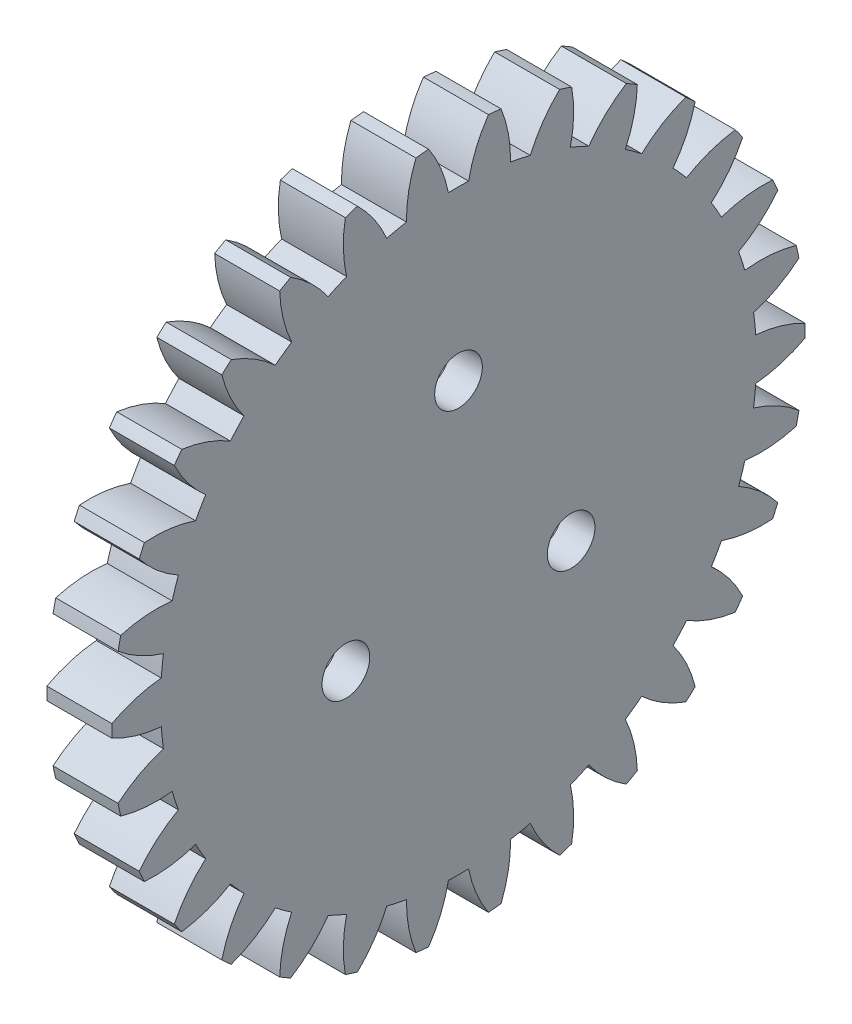
SolidWorks part; units mm, degrees
material "ﾎﾟﾘｵｷｼﾒﾁﾚﾝ(POM)ｱｾﾀｰﾙ共重合体"
ref_plane "Plane1" through (0, 0, 0) normal (0, 0, 1) x (1, 0, 0)
ref_plane "Plane2" through (0, 0, 0) normal (0, 1, 0) x (1, 0, 0)
ref_plane "Plane3" through (0, 0, 0) normal (1, 0, 0) x (0, 0, -1)
other "Configuration Table"
sketch "HoldingSke" plane through (0, 0, 0) normal (0, 1, 0) x (1, 0, 0)
  line L0 (0, 0) -> (0.866, -0.5)
  line L1 (-15, 0) -> (100, 0) construction
  line L2 (0, 0) -> (-2.1039, 2.3779)
  line L3 (0, 0) -> (-11.863, 4.5341)
  line L4 (0, 0) -> (7.479, 4.318)
  line L5 (0, 0) -> (-46.8476, -17.4728)
  line L6 (0, 0) -> (-2.4869, -1.6779)
  line L7 (-2.1039, 2.3779) -> (8.6586, 51.2059)
  line L8 (-76.2, 54.61) -> (-75.2, 54.61)
  line L9 (-71.009, 38.7566) -> (-53.1078, 45.2721)
  line L10 (-76.2, 71.12) -> (104.1128, 71.12)
  line L11 (0, 0) -> (-3, 0)
  line L12 (-76.2, 101.6) -> (-76.162, 101.6)
  line L13 (24.9733, 27.94) -> (52.9518, 28.4284)
  line L14 (24.9733, 27.94) -> (24.9743, 27.94)
  line L15 (24.9733, 27.94) -> (100.4006, 29.5858)
  line L16 (-63.627, -1) -> (-12.827, -1)
  circle A0 centre (0, 0) radius 4
  circle A1 centre (0, 0) radius 13.749
  circle A2 centre (0, 0) radius 37.5
  circle A3 centre (0, 0) radius 4
  dimension "MHD" = 27.498
  dimension "Hub_dia" = 75
  dimension "Bore" = 8
  dimension "MBD" = 8
  dimension "Num_teeth" = 30
  dimension "Pitch" = 1
  dimension "Overall_len" = 50
  dimension "Show_teeth" = 30
  dimension "Thickness" = 3
  dimension "OAL" = 50.0001
  dimension "T_dim" = 1
  dimension "Ap" = 20
  dimension "H" = 19.05
  dimension "Pitch_radius" = 180.3128
  dimension "Width" = 3
  dimension "Backlash" = 0.038
  dimension "Addendum_fac" = 1
  dimension "Dedendum_fac" = 1.25
  dimension "Clearance_fac" = 0.25
  dimension "Dedendum_add" = 0.001
  dimension "Module" = 1
sketch "BasProSke" plane through (0, 0, 0) normal (0, 1, 0) x (1, 0, 0)
  line L0 (-10, 0) -> (60, 0) construction
  line L1 (0, 0) -> (0, 16)
  line L2 (0, 0) -> (3, 0)
  line L3 (3, 0) -> (3, 16)
  line L4 (3, 16) -> (0, 16)
  dimension "Thickness" = 3
  dimension "Diameter" = 32
revolve "Base-Revolve" add sketch "BasProSke" angle 360 about L0
sketch "TooCutSke" plane through (0, 0, 0) normal (1, 0, 0) x (0, 0, -1)
  line L1 (0, 0) -> (0, 107) construction
  line L2 (0, 0) -> (-0.8515, 14.9758) construction
  line L3 (0, 0) -> (-3.1323, 29.8014) construction
  line L4 (-0.8515, 14.9758) -> (-1.5661, 14.9007) construction
  arc A0 (0.4664, 13.7411) -> (-0.4664, 13.7411) centre (0, 0) ccw
  arc A1 (1.3975, 15.9644) -> (-1.3975, 15.9644) centre (0, 0) ccw
  circle A2 centre (0, 0) radius 15 construction
  circle A3 centre (0, 0) radius 14.0954 construction
  arc A4 (-0.4664, 13.7411) -> (-1.3975, 15.9644) centre (-6.3534, 12.5823) ccw
  arc A5 (1.3975, 15.9644) -> (0.4664, 13.7411) centre (6.3534, 12.5823) ccw
  dimension "Root_dia" = 27.498
  dimension "Overcut_dia" = 32.0508
  dimension "Pitch_dia" = 30
  dimension "Base_dia" = 28.1908
  dimension "Flank_rad" = 6
  dimension "Half_ang" = 6
  dimension "Half_CT" = 0.7185
extrude "ToothCut" cut sketch "TooCutSke" along normal through all
fillet "Breaks" [suppressed] radius 0.02 tangent propagation no
fillet "RootFillets" [suppressed] radius 0.251
pattern_circular "TeethCuts" count 30 every 12 about axis through (-10, 0, 0) along (1, 0, 0) of "ToothCut", "RootFillets", "Breaks"
sketch "HubNeaOneSke" plane through (0, 0, 0) normal (-1, 0, 0) x (0, 0, 1)
  circle A0 centre (0, 0) radius 13.749
  dimension "Diameter" = 27.498
extrude "HubNearOne" [suppressed] add sketch "HubNeaOneSke" along normal blind 47.0001
sketch "HubNeaBotSke" plane through (0, 0, 0) normal (-1, 0, 0) x (0, 0, 1)
  circle A0 centre (0, 0) radius 13.749
  dimension "Diameter" = 27.498
extrude "HubNearBoth" [suppressed] add sketch "HubNeaBotSke" along normal blind 23.5
ref_plane "FarPln" through (3, 0, 0) normal (1, 0, 0) x (0, 0, -1)
sketch "HubFarSke" plane through (3, 0, 0) normal (1, 0, 0) x (0, 0, -1)
  circle A0 centre (0, 0) radius 13.749
  dimension "Diameter" = 27.498
extrude "HubFar" [suppressed] add sketch "HubFarSke" along normal blind 23.5
sketch "BorSke" plane through (0, 0, 0) normal (1, 0, 0) x (0, 0, -1)
  circle A0 centre (0, 0) radius 4
  dimension "Diameter" = 8
extrude "Bore" cut sketch "BorSke" along normal mid plane 100.0001
sketch "KeySke" plane through (0, 0, 0) normal (1, 0, 0) x (0, 0, -1)
  line L0 (-1, 0) -> (-1, 5)
  line L1 (-1, 5) -> (1, 5)
  line L2 (1, 5) -> (1, 0)
  line L3 (0, 0) -> (0, 34) construction
  line L4 (-1, 0) -> (1, 0)
  dimension "Offset" = 5
  dimension "Width" = 2
extrude "Keyway" [suppressed] cut sketch "KeySke" along normal mid plane 100.0001
pattern_circular "Keyway2" [suppressed] count 2 every 90 about axis through (-10, 0, 0) along (1, 0, 0) reverse direction yes
sketch "ｽｹｯﾁ1" plane through (0, 0, 0) normal (-1, 0, 0) x (0, 0, 1)
  circle A0 centre (0, 0) radius 4 construction
  circle A1 centre (0, 0) radius 4
extrude "ﾎﾞｽ - 押し出し1" add sketch "ｽｹｯﾁ1" against normal up to surface (3 mm away) up to face at (3, 0, 4)
sketch "ｽｹｯﾁ2" plane through (0, 0, 0) normal (-1, 0, 0) x (0, 0, 1)
  circle A0 centre (0, 0) radius 6 construction
  circle A1 centre (0, 6) radius 1.1
  circle A2 centre (5.1962, -3) radius 1.1
  circle A3 centre (-5.1962, -3) radius 1.1
  point P11 (0, 0)
  dimension "D1" = 12
  dimension "D2" = 2.2
  dimension "D3" = 3
extrude "ｶｯﾄ - 押し出し1" cut sketch "ｽｹｯﾁ2" against normal through all
sketch "ｽｹｯﾁ3" plane through (0, 0, 0) normal (-1, 0, 0) x (0, 0, 1)
  circle A0 centre (0, 6) radius 2.5
  circle A1 centre (5.1962, -3) radius 2.5
  circle A2 centre (-5.1962, -3) radius 2.5
  circle A3 centre (-5.1962, -3) radius 1.1 construction
  point P9 (0, 0)
  dimension "D1" = 5
  dimension "D2" = 3
extrude "ｶｯﾄ - 押し出し2" cut sketch "ｽｹｯﾁ3" against normal blind 1.5
equation "' \"Module@HoldingSke\" = 6.35"
equation "' \"Num_teeth@HoldingSke\" = 12"
equation "' \"Ap@HoldingSke\" =  20"
equation "' \"Ap@HoldingSke\" = 20"
equation "' \"Width@HoldingSke\" = 0.5 * 25.4"
equation "' \"Hub_dia@HoldingSke\"= 1 * 25.4"
equation "' \"Hub_dia@HoldingSke\" = 1 * 25.4"
equation "' \"Overall_len@HoldingSke\" = 1.0 * 25.4"
equation "' \"Bore@HoldingSke\" = 0.75 * 25.4"
equation "' \"T_dim@HoldingSke\" = 0.1 * 25.4"
equation "' \"Width@KeySke\" = 0.25 * 25.4"
equation "' \"Show_teeth@HoldingSke\" = 13"
equation "' \"Backlash@HoldingSke\" = 0.009 * 25.4"
equation "' \"Addendum_fac@HoldingSke\" = 1.0"
equation "' \"Dedendum_fac@HoldingSke\" = 1.25"
equation "' \"Dedendum_add@HoldingSke\" = 0.00005 * 25.4"
equation "' \"Clearance_fac@HoldingSke\" = 0.25"
equation "\"Pitch@HoldingSke\" = 1 / \"Module@HoldingSke\""
equation "\"Overcut_dia@TooCutSke\" = (\"Num_teeth@HoldingSke\" + 2 * \"Addendum_fac@HoldingSke\") / \"Pitch@HoldingSke\" + 0.002 * 25.4"
equation "\"Pitch_dia@TooCutSke\" = \"Num_teeth@HoldingSke\" / \"Pitch@HoldingSke\""
equation "\"Base_dia@TooCutSke\" = \"Num_teeth@HoldingSke\" / \"Pitch@HoldingSke\" * cos((\"Ap@HoldingSke\"  * 3.14159265 / 180))"
equation "\"Root_dia@TooCutSke\" = (\"Num_teeth@HoldingSke\" + 2) / \"Pitch@HoldingSke\" - 2 * (\"Addendum_fac@HoldingSke\" + \"Dedendum_fac@HoldingSke\") / \"Pitch@HoldingSke\" - \"Dedendum_add@HoldingSke\" * 2"
equation "\"Half_ang@TooCutSke\" = 180 / \"Num_teeth@HoldingSke\""
equation "\"Half_CT@TooCutSke\" = \"Num_teeth@HoldingSke\" / \"Pitch@HoldingSke\" * sin((3.14159265 / 2 / \"Num_teeth@HoldingSke\")) / 2 - 7 * \"Backlash@HoldingSke\" / 4"
equation "\"Flank_rad@TooCutSke\" = \"Num_teeth@HoldingSke\" / \"Pitch@HoldingSke\" / 5"
equation "\"Radius@RootFillets\" = \"Clearance_fac@HoldingSke\" / \"Pitch@HoldingSke\" + \"Dedendum_add@HoldingSke\""
equation "\"Break_rad@Breaks\" = 0.02 / \"Pitch@HoldingSke\""
equation "\"Thickness@HoldingSke\" = \"Width@HoldingSke\""
equation "\"OAL@HoldingSke\" = \"Thickness@HoldingSke\""
equation "\"MHD@HoldingSke\" = (\"Num_teeth@HoldingSke\" + 2) / \"Pitch@HoldingSke\" - 2 * (\"Addendum_fac@HoldingSke\" + \"Dedendum_fac@HoldingSke\")  / \"Pitch@HoldingSke\" - \"Dedendum_add@HoldingSke\" * 2"
equation "\"MBD@HoldingSke\" = (\"Num_teeth@HoldingSke\" + 2) / \"Pitch@HoldingSke\" - 2 * (\"Addendum_fac@HoldingSke\" + \"Dedendum_fac@HoldingSke\")  / \"Pitch@HoldingSke\" - \"Dedendum_add@HoldingSke\" * 2 - 0.002 * 25.4"
equation "\"MHD@HoldingSke\" = ((sgn( \"MHD@HoldingSke\" - \"Hub_dia@HoldingSke\" )-1)*( \"MHD@HoldingSke\" - \"Hub_dia@HoldingSke\" ))/-2+ \"Hub_dia@HoldingSke\""
equation "\"MBD@HoldingSke\" = ((sgn( \"MBD@HoldingSke\" - \"Bore@HoldingSke\" )-1)*( \"MBD@HoldingSke\" - \"Bore@HoldingSke\" ))/-2+ \"Bore@HoldingSke\""
equation "\"OAL@HoldingSke\" = ((sgn( \"OAL@HoldingSke\" - \"Overall_len@HoldingSke\" )+1)*( \"OAL@HoldingSke\" - \"Overall_len@HoldingSke\" ))/2 + \"Overall_len@HoldingSke\" + 0.000002 * 25.4"
equation "\"Num_teeth@TeethCuts\" = int( \"Show_teeth@HoldingSke\" ) + 1"
equation "\"Num_teeth@TeethCuts\" = ((sgn( \"Num_teeth@TeethCuts\" - \"Num_teeth@HoldingSke\" )-1)*( \"Num_teeth@TeethCuts\" - \"Num_teeth@HoldingSke\" ))/-2+ \"Num_teeth@HoldingSke\""
equation "\"Num_teeth@TeethCuts\" = ((sgn( \"Num_teeth@TeethCuts\" - 2.0)+1)*( \"Num_teeth@TeethCuts\" - 2.0))/2 +2.0"
equation "\"Angle@TeethCuts\" = 360.0 / \"Num_teeth@HoldingSke\""
equation "\"Diameter@BasProSke\" = (\"Num_teeth@HoldingSke\" + 2 * \"Addendum_fac@HoldingSke\") / \"Pitch@HoldingSke\""
equation "\"Thickness@BasProSke\"  = \"Thickness@HoldingSke\""
equation "' \"Fillet_rad@BasProSke\" =  \"Thickness@HoldingSke\" * 0.05"
equation "' \"Fillet_rad@BasProSke\" = \"Thickness@HoldingSke\" * 0.05"
equation "\"MHD@HoldingSke\" = ((sgn( \"MHD@HoldingSke\" - \"Root_dia@TooCutSke\" )-1)*( \"MHD@HoldingSke\" - \"Root_dia@TooCutSke\" ))/-2+ \"Root_dia@TooCutSke\""
equation "\"Diameter@HubNeaOneSke\" = \"MHD@HoldingSke\""
equation "\"Length@HubNearOne\" = \"OAL@HoldingSke\" - \"Thickness@BasProSke\""
equation "\"Diameter@HubNeaBotSke\" = \"MHD@HoldingSke\""
equation "\"Length@HubNearBoth\" = ( \"OAL@HoldingSke\" - \"Thickness@BasProSke\" ) / 2.0"
equation "\"Thickness@FarPln\" = \"Thickness@BasProSke\""
equation "\"Diameter@HubFarSke\" = \"MHD@HoldingSke\""
equation "\"Length@HubFar\" = ( \"OAL@HoldingSke\" - \"Thickness@BasProSke\" ) / 2.0"
equation "\"Diameter@BorSke\" = \"MBD@HoldingSke\""
equation "\"D1@Bore\" = \"OAL@HoldingSke\" * 2.0"
equation "\"D1@Keyway\" = \"OAL@HoldingSke\" * 2.0"
equation "\"Offset@KeySke\" = \"T_dim@HoldingSke\" + \"MBD@HoldingSke\" / 2.0"
